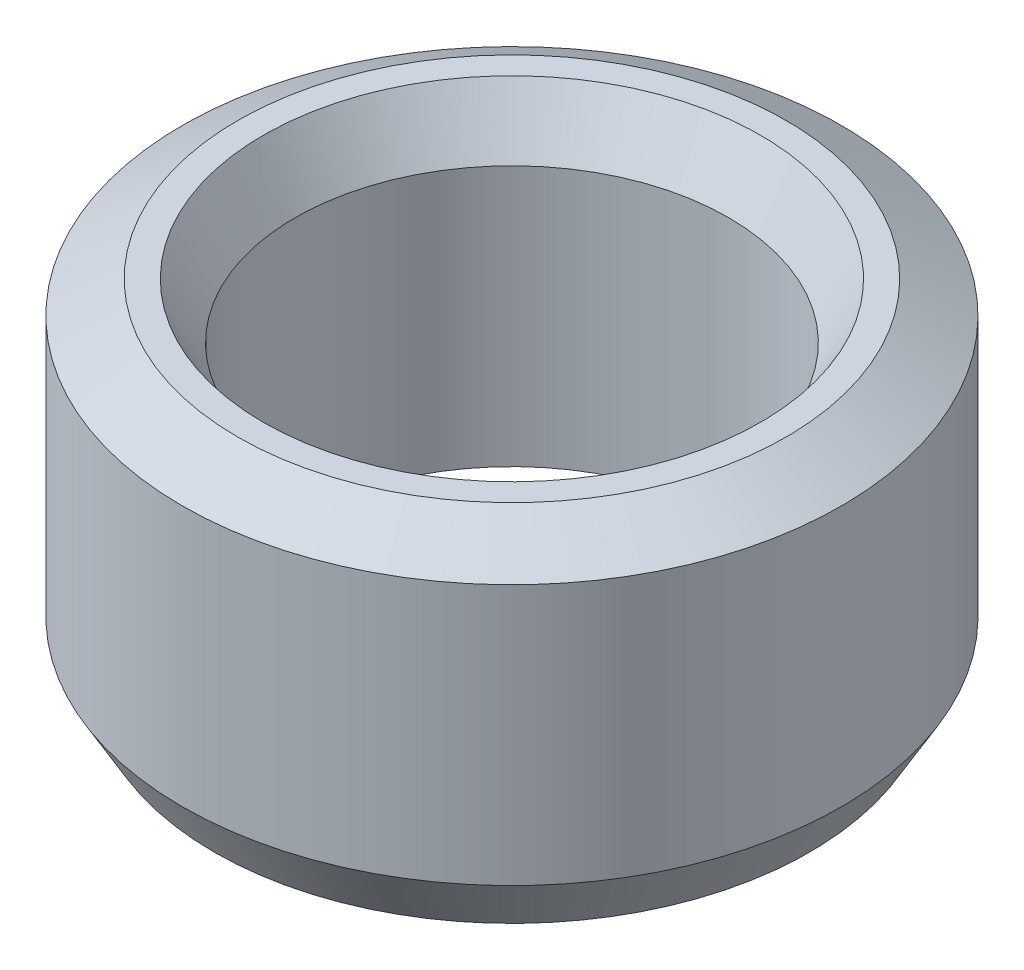
SolidWorks part; units mm, degrees
ref_plane "Front Plane" through (0, 0, 0) normal (0, 0, 1) x (1, 0, 0)
ref_plane "Top Plane" through (0, 0, 0) normal (0, 1, 0) x (1, 0, 0)
ref_plane "Right Plane" through (0, 0, 0) normal (1, 0, 0) x (0, 0, -1)
sketch "Sketch1" plane through (0, 0, 0) normal (0, 1, 0) x (1, 0, 0)
  circle A0 centre (0, 0) radius 35
  dimension "SLEEVE_OD" = 70
extrude "Boss-Extrude1" add sketch "Sketch1" along normal blind 36.9426
sketch "Sketch2" plane through (0, 0, 0) normal (0, 1, 0) x (1, 0, 0)
  circle A0 centre (0, 0) radius 23.0123
  dimension "BORE_D" = 46.0245
extrude "Cut-Extrude1" cut sketch "Sketch2" along normal through all
chamfer "Chamfer1" distance 3.3946 angle 60 4 edges at (0, 36.9426, 23.0123) (0, 0, 23.0123) (0, 0, 35) (0, 36.9426, 35) first distance on face at (0, 36.9426, 23.0123) first distance on face at (0, 0, 23.0123) first distance on face at (0, 36.9426, 35)
